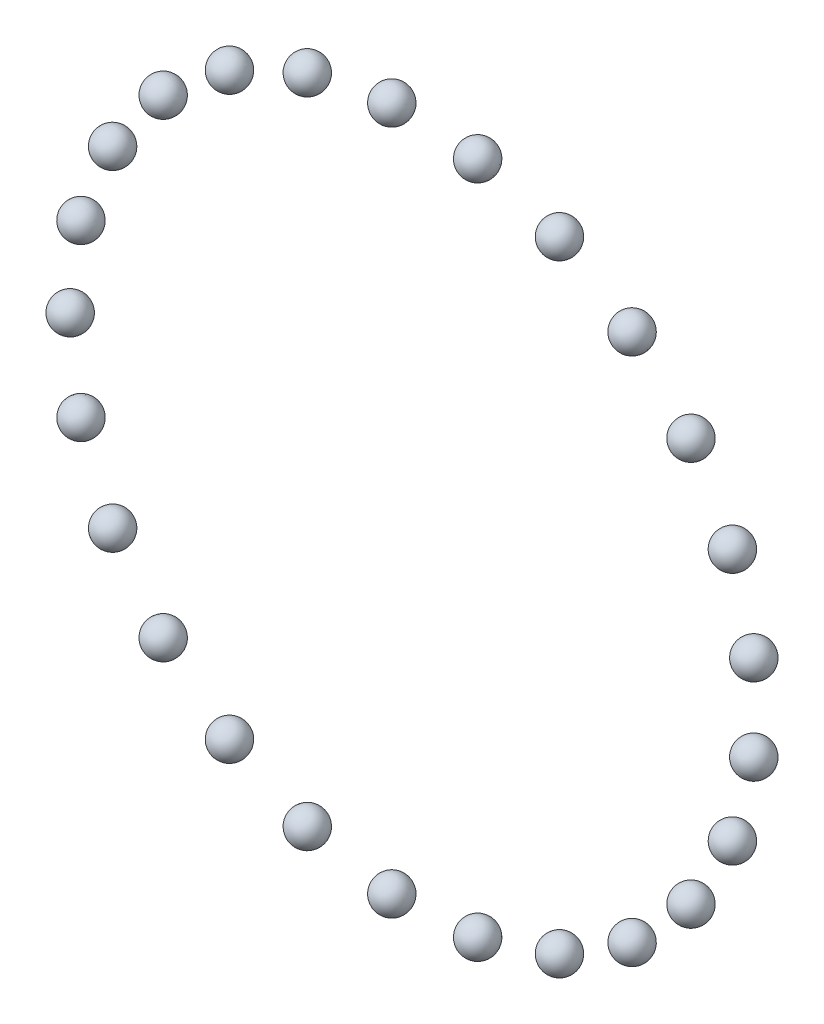
SolidWorks part; units mm, degrees
ref_plane "Front Plane" through (0, 0, 0) normal (0, 0, 1) x (1, 0, 0)
ref_plane "Top Plane" through (0, 0, 0) normal (0, 1, 0) x (1, 0, 0)
ref_plane "Right Plane" through (0, 0, 0) normal (1, 0, 0) x (0, 0, -1)
sketch "Sketch1" plane through (0, 0, 0) normal (0, 0, 1) x (1, 0, 0)
  line L0 (-84, 0) -> (-76, 0)
  circle A0 centre (0, 0) radius 80 construction
  circle A1 centre (-80, 0) radius 4
  dimension "D1" = 160
  dimension "D2" = 8
revolve "Revolve1" add sketch "Sketch1" angle 360 about L0 region at (-80, 1.6977, 0)
ref_axis "Axis1" through (0, 0, 4.4) along (0, 0, -1)
pattern_circular "CirPattern1" count 25 over 360 about axis through (0, 0, 4.4) along (0, 0, -1) of bodies 101
